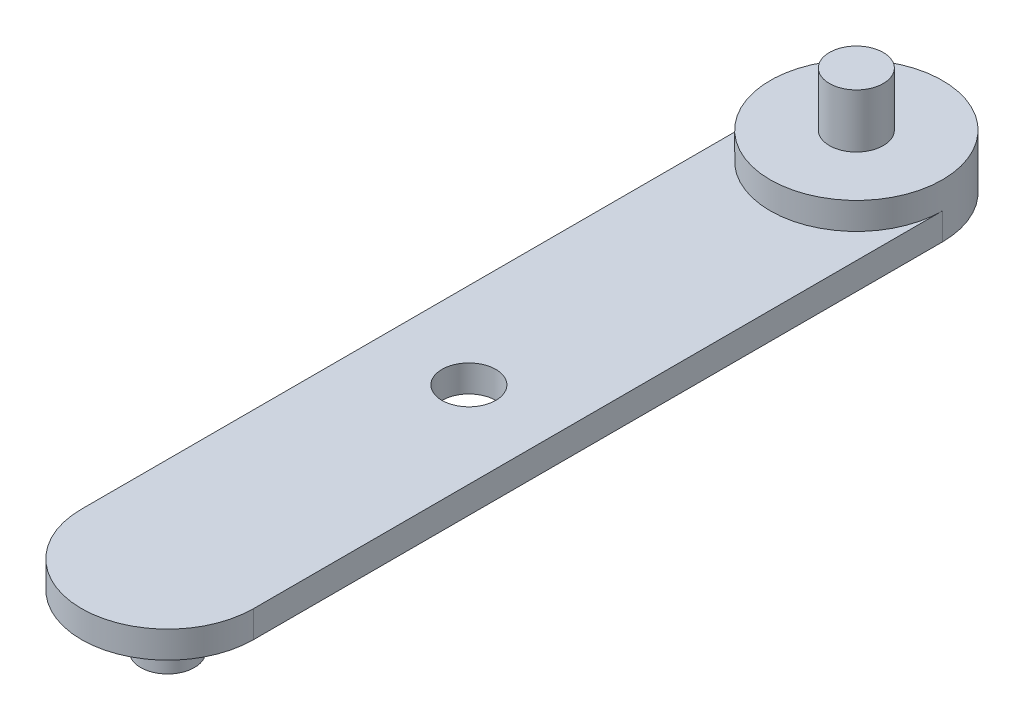
SolidWorks part; units mm, degrees
ref_plane "Front Plane" through (0, 0, 0) normal (0, 0, 1) x (1, 0, 0)
ref_plane "Top Plane" through (0, 0, 0) normal (0, 1, 0) x (1, 0, 0)
ref_plane "Right Plane" through (0, 0, 0) normal (1, 0, 0) x (0, 0, -1)
sketch "Sketch1" plane through (0, 0, 0) normal (0, 1, 0) x (1, 0, 0)
  line L0 (0, 0) -> (0, 32) construction
  line L1 (-4, 0) -> (-4, 32)
  line L2 (4, 0) -> (4, 32)
  arc A0 (-4, 0) -> (4, 0) centre (0, 0) ccw
  arc A1 (4, 32) -> (-4, 32) centre (0, 32) ccw
  circle A2 centre (0, 32) radius 4
  point P3 (0, 16)
  dimension "D1" = 32
  dimension "D2" = 4
extrude "Boss-Extrude1" add sketch "Sketch1" along normal blind 2.5 contours A1 A2 region at (0, 0, -32)
extrude "Boss-Extrude5" add sketch "Sketch1<4>" along normal blind 1.25 contours A2 L1 A0 L2 region at (0, 0, -12.8584)
sketch "Sketch1<4>" plane through (0, 0, 0) normal (0, 1, 0) x (1, 0, 0) same geometry as "Sketch1"
sketch "Sketch6" plane through (0, 2.5, 0) normal (0, 1, 0) x (1, 0, 0)
  circle A0 centre (0, 32) radius 1.25
  point P3 (0, 0)
  dimension "D1" = 2.5
extrude "Boss-Extrude6" add sketch "Sketch6" along normal blind 2.5
sketch "Sketch7" plane through (0, 0, 0) normal (0, -1, 0) x (1, 0, 0)
  circle A0 centre (0, 0) radius 1.25
  dimension "D1" = 2.5
extrude "Boss-Extrude7" add sketch "Sketch7" along normal blind 2.5
sketch "Sketch8" plane through (0, 1.25, 0) normal (0, 1, 0) x (1, 0, 0)
  circle A0 centre (0, 14) radius 1.25
  point P2 (0, 0)
  dimension "D1" = 2.5
  dimension "D2" = 14
extrude "Cut-Extrude3" cut sketch "Sketch8" against normal blind 2.5
